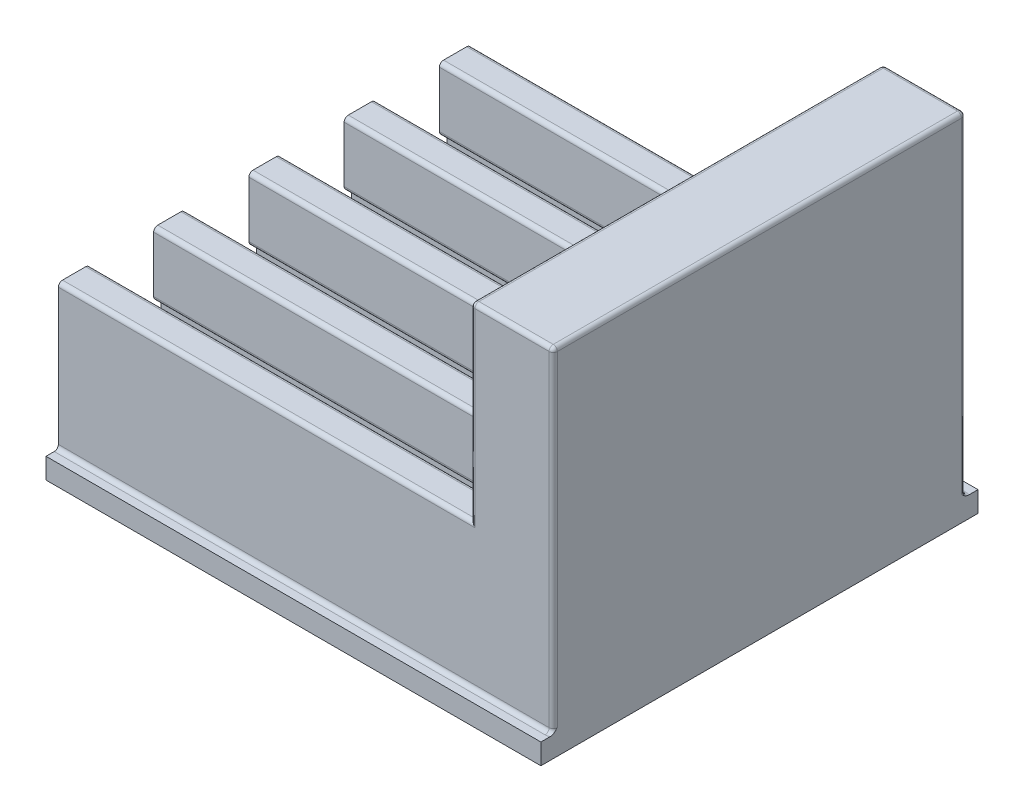
SolidWorks part; units mm, degrees
ref_plane "Front Plane" through (0, 0, 0) normal (0, 0, 1) x (1, 0, 0)
ref_plane "Top Plane" through (0, 0, 0) normal (0, 1, 0) x (1, 0, 0)
ref_plane "Right Plane" through (0, 0, 0) normal (1, 0, 0) x (0, 0, -1)
sketch "Sketch1" plane through (0, 0, 0) normal (0, 1, 0) x (1, 0, 0)
  line L1 (-63.5354, 42.4181) -> (56.4646, 42.4181)
  line L2 (-63.5354, 42.4181) -> (-63.5354, -57.5819)
  line L3 (-63.5354, -57.5819) -> (56.4646, -57.5819)
  line L4 (56.4646, 42.4181) -> (56.4646, -57.5819)
  dimension "D1" = 100
  dimension "D2" = 120
extrude "Boss-Extrude1" add sketch "Sketch1" along normal blind 81
sketch "Sketch2" plane through (0, 81, 0) normal (0, 1, 0) x (1, 0, 0)
  line L0 (-63.5354, -57.5819) -> (56.4646, -57.5819) construction
  line L1 (-63.5354, 42.4181) -> (36.4646, 42.4181)
  line L2 (-63.5354, 42.4181) -> (-63.5354, -57.5819)
  line L3 (-63.5354, -57.5819) -> (36.4646, -57.5819)
  line L4 (36.4646, 42.4181) -> (36.4646, -57.5819)
  dimension "D1" = 100
extrude "Cut-Extrude1" cut sketch "Sketch2" against normal blind 46
sketch "Sketch6" plane through (-63.5354, 0, 0) normal (-1, 0, 0) x (0, 0, 1)
  line L0 (57.5819, 35) -> (-42.4181, 35) construction
  line L1 (-34.8181, 35) -> (-19.3181, 35)
  line L2 (-34.8181, 35) -> (-34.8181, 19.5)
  line L3 (-34.8181, 19.5) -> (-19.3181, 19.5)
  line L4 (-19.3181, 35) -> (-19.3181, 19.5)
  line L5 (-19.3181, 27.25) -> (-11.7181, 27.25) construction
  line L6 (-11.7181, 35) -> (3.7819, 35)
  line L7 (-11.7181, 35) -> (-11.7181, 19.5)
  line L8 (-11.7181, 19.5) -> (3.7819, 19.5)
  line L9 (3.7819, 35) -> (3.7819, 19.5)
  line L10 (11.3819, 35) -> (26.8819, 35)
  line L11 (11.3819, 35) -> (11.3819, 19.5)
  line L12 (11.3819, 19.5) -> (26.8819, 19.5)
  line L13 (26.8819, 35) -> (26.8819, 19.5)
  line L14 (34.4819, 35) -> (49.9819, 35)
  line L15 (34.4819, 35) -> (34.4819, 19.5)
  line L16 (34.4819, 19.5) -> (49.9819, 19.5)
  line L17 (49.9819, 35) -> (49.9819, 19.5)
  line L18 (-15.5181, 27.25) -> (-15.5181, 0) construction
  line L19 (-42.4181, 0) -> (57.5819, 0) construction
  line L20 (7.5819, 35) -> (7.5819, 0) construction
  line L21 (-42.4181, 35) -> (57.5819, 35) construction
  circle A0 centre (-27.0681, 27.25) radius 5.95
  circle A1 centre (-3.9681, 27.25) radius 5.95
  circle A2 centre (42.2319, 27.25) radius 5.95
  circle A3 centre (19.1319, 27.25) radius 5.95
  dimension "D13" = 7.75
  dimension "D1" = 15.5
  dimension "D2" = 15.5
  dimension "D3" = 15.5
  dimension "D4" = 15.5
  dimension "D5" = 15.5
  dimension "D6" = 15.5
  dimension "D7" = 15.5
  dimension "D8" = 15.5
  dimension "D9" = 7.6
  dimension "D10" = 7.6
  dimension "D11" = 7.6
  dimension "D12" = 7.6
  dimension "D14" = 7.75
extrude "Cut-Extrude4" cut sketch "Sketch6" against normal blind 100 contours L11 L10 L13 L12 | L15 L14 L17 L16 | L7 L6 L9 L8 | L2 L1 L4 L3
sketch "Sketch8" plane through (-63.5354, 0, 0) normal (-1, 0, 0) x (0, 0, 1)
  line L1 (-36.6181, 19.5) -> (-17.5181, 19.5)
  line L2 (-36.6181, 19.5) -> (-36.6181, 9.5)
  line L3 (-36.6181, 9.5) -> (-17.5181, 9.5)
  line L4 (-17.5181, 19.5) -> (-17.5181, 9.5)
  line L6 (-15.5181, 35) -> (-15.5181, 0) construction
  line L7 (-19.3181, 35) -> (-11.7181, 35) construction
  line L8 (-42.4181, 0) -> (57.5819, 0) construction
  line L9 (5.5819, 9.5) -> (-13.5181, 9.5)
  line L10 (-13.5181, 19.5) -> (-13.5181, 9.5)
  line L11 (5.5819, 19.5) -> (-13.5181, 19.5)
  line L12 (5.5819, 19.5) -> (5.5819, 9.5)
  line L13 (7.5819, 35) -> (7.5819, 0) construction
  line L14 (11.3819, 35) -> (3.7819, 35) construction
  line L15 (51.7819, 9.5) -> (32.6819, 9.5)
  line L16 (32.6819, 19.5) -> (32.6819, 9.5)
  line L17 (51.7819, 19.5) -> (32.6819, 19.5)
  line L18 (51.7819, 19.5) -> (51.7819, 9.5)
  line L19 (9.5819, 19.5) -> (9.5819, 9.5)
  line L20 (9.5819, 19.5) -> (28.6819, 19.5)
  line L21 (28.6819, 19.5) -> (28.6819, 9.5)
  line L22 (9.5819, 9.5) -> (28.6819, 9.5)
  dimension "D1" = 1.8
  dimension "D2" = 10
  dimension "D3" = 19.1
extrude "Cut-Extrude5" cut sketch "Sketch8" against normal blind 100
extrude "Cut-Extrude6" cut sketch "Sketch6<3>" against normal blind 111 contours A0 | A1 | A3 | A2 region at (-63.5354, 27.25, -27.0681) region at (-63.5354, 27.25, -3.9681) region at (-63.5354, 27.25, 42.2319) region at (-63.5354, 27.25, 19.1319)
sketch "Sketch6<3>" plane through (-63.5354, 0, 0) normal (-1, 0, 0) x (0, 0, 1) same geometry as "Sketch6"
fillet "Fillet1" radius 1 10 edges at (-13.5354, 35, -42.4181) (-13.5354, 35, 57.5819) (36.4646, 58, -42.4181) (36.4646, 58, 57.5819) (46.4646, 81, 57.5819) (36.4646, 81, 7.5819) (46.4646, 81, -42.4181) (56.4646, 81, 7.5819) (56.4646, 40.5, 57.5819) (56.4646, 40.5, -42.4181)
chamfer "Chamfer1" distance 1 angle 45 4 edges at (36.4646, 27.25, 36.2819) (36.4646, 27.25, 13.1819) (36.4646, 27.25, -9.9181) (36.4646, 27.25, -33.0181)
fillet "Fillet2" radius 1 4 edges at (47.4646, 27.25, 48.1819) (47.4646, 27.25, 25.0819) (47.4646, 27.25, 1.9819) (47.4646, 27.25, -21.1181)
fillet "Fillet3" radius 1 16 edges at (-13.5354, 19.5, -19.3181) (-13.5354, 19.5, 3.7819) (-13.5354, 19.5, 26.8819) (-13.5354, 19.5, -34.8181) (-13.5354, 19.5, -11.7181) (-13.5354, 19.5, 11.3819) (-13.5354, 19.5, 34.4819) (-13.5354, 19.5, 49.9819) (-13.5354, 35, -34.8181) (-13.5354, 35, -19.3181) (-13.5354, 35, -11.7181) (-13.5354, 35, 3.7819) (-13.5354, 35, 26.8819) (-13.5354, 35, 11.3819) (-13.5354, 35, 34.4819) (-13.5354, 35, 49.9819)
sketch "Sketch9" plane through (0, 0, 0) normal (0, -1, 0) x (1, 0, 0)
  line L0 (56.4646, 56.5819) -> (56.4646, -41.4181) construction
  line L1 (-63.5354, 60.5819) -> (56.4646, 60.5819)
  line L2 (-63.5354, 60.5819) -> (-63.5354, -45.4181)
  line L3 (-63.5354, -45.4181) -> (56.4646, -45.4181)
  line L4 (56.4646, 60.5819) -> (56.4646, -45.4181)
  line L5 (-63.5354, -42.4181) -> (-63.5354, 57.5819) construction
  line L6 (-63.5354, 57.5819) -> (55.4646, 57.5819) construction
  line L7 (55.4646, -42.4181) -> (-63.5354, -42.4181) construction
  dimension "D1" = 3
  dimension "D2" = 3
extrude "Boss-Extrude2" add sketch "Sketch9" along normal blind 5
fillet "Fillet4" radius 1 4 edges at (56.1717, 0, 57.289) (56.1717, 0, -42.1252) (-4.0354, 0, 57.5819) (-4.0354, 0, -42.4181)
